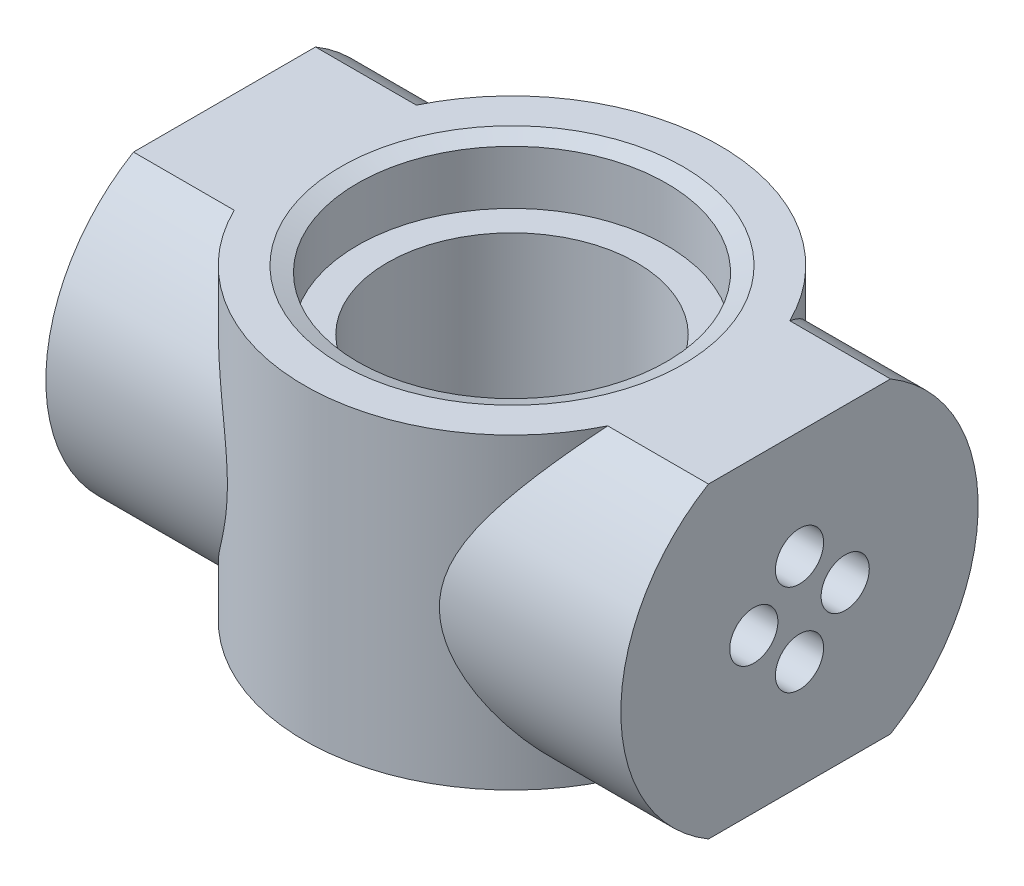
SolidWorks part; units mm, degrees
ref_plane "Ebene vorne" through (0, 0, 0) normal (0, 0, 1) x (1, 0, 0)
ref_plane "Ebene oben" through (0, 0, 0) normal (0, 1, 0) x (1, 0, 0)
ref_plane "Ebene rechts" through (0, 0, 0) normal (1, 0, 0) x (0, 0, -1)
ref_plane "Ebene1" through (18.6, 0, 0) normal (1, 0, 0) x (0, 0, -1)
sketch "Skizze1" plane through (0, 0, 0) normal (0, 1, 0) x (1, 0, 0)
  circle A0 centre (0, 0) radius 25
  circle A1 centre (0, 0) radius 18.6
  dimension "D1" = 50
  dimension "D2" = 37.2
extrude "Aufsatz-Linear austragen1" add sketch "Skizze1" along normal mid plane 37
sketch "Skizze2" plane through (0, 0, 0) normal (0, 1, 0) x (1, 0, 0)
  circle A0 centre (0, 0) radius 15
  circle A5 centre (0, 0) radius 18.6
  circle A6 centre (0, 0) radius 18.6 construction
  dimension "D2" = 30
extrude "Aufsatz-Linear austragen2" add sketch "Skizze2" along normal mid plane 22.6
sketch "Skizze3" plane through (18.6, 0, 0) normal (1, 0, 0) x (0, 0, -1)
  line L9 (-25, -18.5) -> (25, -18.5) construction
  circle A2 centre (0, 0) radius 21.5
  dimension "D1" = 3
extrude "Aufsatz-Linear austragen3" add sketch "Skizze3" along normal blind 16
sketch "Skizze4" plane through (34.6, 0, 0) normal (1, 0, 0) x (0, 0, -1)
  line L0 (0, 0) -> (-5.5, 0) construction
  circle A0 centre (-5.5, 0) radius 2.9
  circle A1 centre (0, 5.5) radius 2.9
  circle A2 centre (5.5, 0) radius 2.9
  circle A3 centre (0, -5.5) radius 2.9
  point P13 (0, 0)
  dimension "D2" = 5.8
  dimension "D1" = 5.5
  dimension "D3" = 4
extrude "Schnitt-Linear austragen1" cut sketch "Skizze4" against normal blind 9.1
mirror "Spiegeln1" about plane through (0, 0, 0) normal (1, 0, 0) of "Schnitt-Linear austragen1", "Aufsatz-Linear austragen3"
sketch "Skizze5" plane through (0, 29.286, 0) normal (-1, 0, 0) x (0, -1, 0)
  line L1 (10.786, 25) -> (47.786, 25)
  line L2 (10.786, 25) -> (10.786, -25)
  line L3 (10.786, -25) -> (47.786, -25)
  line L4 (47.786, 25) -> (47.786, -25)
  line L5 (47.786, 25) -> (10.786, 25) construction
  line L6 (10.786, 25) -> (10.786, 10.9545) construction
extrude "Schnitt-Linear austragen2" cut sketch "Skizze5" against normal through all both and the other way through all flip side to cut
ref_axis "Achse1" through (31.35, 0, 0) along (-1, 0, 0)
ref_axis "Achse2" through (0, -20.35, 0) along (0, 1, 0)
sketch "Skizze7" plane through (18.6, 0, 0) normal (-1, 0, 0) x (0, 0, 1)
  line L0 (16.7045, 13.5355) -> (16.7045, -13.5355)
  line L1 (16.7045, 13.5355) -> (16.7045, -13.5355) construction
  arc A0 (16.7045, -13.5355) -> (16.7045, 13.5355) centre (0, 0) ccw construction
  arc A1 (16.7045, -13.5355) -> (16.7045, 13.5355) centre (0, 0) ccw
  point P7 (17.0137, -13.1447)
extrude "Aufsatz-Linear austragen4" add sketch "Skizze7" along normal up to surface (37.2 mm away)
mirror "Spiegeln2" about plane through (0, 0, 0) normal (0, 0, 1) of "Aufsatz-Linear austragen4"
sketch "Skizze8" plane through (0, 11.3, 0) normal (0, 1, 0) x (1, 0, 0)
  circle A1 centre (0, 0) radius 18.6
  circle A2 centre (0, 0) radius 18.6
  dimension "D1" = 0
extrude "Schnitt-Linear austragen3" cut sketch "Skizze8" along normal through all
mirror "Spiegeln3" about plane through (0, 0, 0) normal (0, 1, 0) of "Schnitt-Linear austragen3"
chamfer "Fase1" distance 2 angle 20 2 edges at (0, 18.5, 18.6) (0, -18.5, 18.6) first distance on face at (0, 18.5, 0) first distance on face at (0, -11.3, 18.6)
